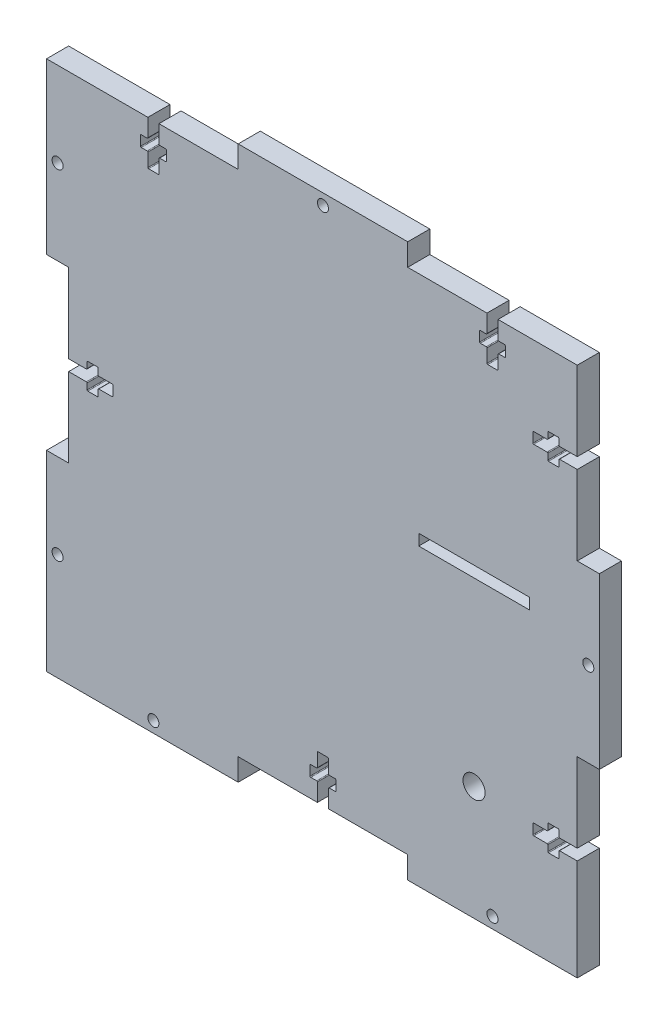
SolidWorks part; units mm, degrees
ref_plane "Front Plane" through (0, 0, 0) normal (0, 0, 1) x (1, 0, 0)
ref_plane "Top Plane" through (0, 0, 0) normal (0, 1, 0) x (1, 0, 0)
ref_plane "Right Plane" through (0, 0, 0) normal (1, 0, 0) x (0, 0, -1)
sketch "Sketch1" plane through (0, 0, 0) normal (0, 0, 1) x (1, 0, 0)
  line L0 (-69, 69) -> (-23, 69)
  line L5 (-75, -75) -> (75, -75) construction
  line L6 (-75, -75) -> (-75, 75) construction
  line L7 (-75, 75) -> (75, 75) construction
  line L8 (75, -75) -> (75, 75) construction
  line L9 (75, 23) -> (69, 23)
  line L10 (69, -23) -> (75, -23)
  line L11 (-69, -69) -> (69, -69) construction
  line L12 (-69, -69) -> (-69, 69) construction
  line L13 (-69, 69) -> (69, 69) construction
  line L14 (69, -69) -> (69, 69) construction
  line L15 (-69, -69) -> (69, 69) construction
  line L16 (69, -69) -> (69, -23)
  line L17 (-23, 69) -> (-23, 75)
  line L18 (-23, 75) -> (23, 75)
  line L19 (23, 75) -> (23, 69)
  line L20 (23, 69) -> (69, 69)
  line L21 (75, -23) -> (75, 23)
  line L22 (69, 23) -> (69, 69)
  line L23 (-75, 23) -> (-69, 23)
  line L24 (-69, 69) -> (-75, 69)
  line L25 (-75, 69) -> (-75, 23)
  line L26 (69, -69) -> (69, -75)
  line L27 (69, -75) -> (23, -75)
  line L28 (23, -75) -> (23, -69)
  line L29 (23, -69) -> (-23, -69)
  line L30 (-23, -69) -> (-23, -75)
  line L31 (-23, -75) -> (-69, -75)
  line L32 (-69, -75) -> (-69, -69) construction
  line L33 (-69, 23) -> (-69, -23)
  line L34 (-69, -23) -> (-75, -23)
  line L35 (-75, -23) -> (-75, -69)
  line L36 (-75, -69) -> (-69, -69) construction
  line L37 (-46, 69) -> (-46, -75) construction
  line L38 (-69, 69) -> (69, -69) construction
  line L39 (-75, -75) -> (-69, -75)
  line L40 (-75, -75) -> (-75, -69)
  point P0 (0, 0)
  point P6 (-7, -7)
  point P26 (0, -75)
  point P27 (-75, 0)
  dimension "D1" = 150
  dimension "D2" = 150
  dimension "D5" = 46
  dimension "D3" = 6
  dimension "D6" = 6
  dimension "D7" = 6
extrude "Box Side" add sketch "Sketch1" along normal blind 6
sketch "Sketch2" plane through (0, 0, 6) normal (0, 0, 1) x (1, 0, 0)
  line L0 (23, 72) -> (-23, 72) construction
  line L1 (23, 75) -> (23, 69) construction
  line L2 (-23, 69) -> (-23, 75) construction
  line L3 (-46, 69) -> (-46, -75) construction
  line L5 (0, 75) -> (0, 69) construction
  line L6 (-23, 75) -> (23, 75) construction
  line L7 (-69, 69) -> (69, 69) construction
  line L16 (-46, 69) -> (-46, -75) construction
  line L21 (0, -69) -> (0, 69) construction
  line L35 (-69, 69) -> (-23, 69) construction
  line L36 (-44.5, 69) -> (-44.5, 64.2)
  line L37 (-44.3, 64) -> (-42.7, 64)
  line L38 (-42.5, 63.8) -> (-42.5, 61.2)
  line L39 (-42.7, 61) -> (-44.3, 61)
  line L40 (-44.5, 60.8) -> (-44.5, 57.2)
  line L46 (-44.7, 57) -> (-47.3, 57)
  line L48 (-44.5, 69) -> (-47.5, 69)
  line L51 (-47.5, 60.8) -> (-47.5, 57.2)
  line L52 (-49.3, 61) -> (-47.7, 61)
  line L53 (-49.5, 63.8) -> (-49.5, 61.2)
  line L54 (-47.7, 64) -> (-49.3, 64)
  line L55 (-47.5, 69) -> (-47.5, 64.2)
  line L56 (47.5, 69) -> (47.5, 64.2)
  line L57 (47.7, 64) -> (49.3, 64)
  line L58 (49.5, 63.8) -> (49.5, 61.2)
  line L59 (49.3, 61) -> (47.7, 61)
  line L60 (47.5, 60.8) -> (47.5, 57.2)
  line L61 (44.5, 69) -> (47.5, 69)
  line L62 (44.7, 57) -> (47.3, 57)
  line L63 (44.5, 60.8) -> (44.5, 57.2)
  line L64 (42.7, 61) -> (44.3, 61)
  line L65 (42.5, 63.8) -> (42.5, 61.2)
  line L66 (44.3, 64) -> (42.7, 64)
  line L67 (44.5, 69) -> (44.5, 64.2)
  line L68 (-69, -69) -> (69, 69) construction
  line L69 (-69, -69) -> (69, 69) construction
  line L70 (75, 0) -> (69, 0) construction
  line L71 (72, 23) -> (72, -23) construction
  line L72 (69, 44.5) -> (64.2, 44.5)
  line L73 (64, 44.3) -> (64, 42.7)
  line L74 (63.8, 42.5) -> (61.2, 42.5)
  line L75 (61, 42.7) -> (61, 44.3)
  line L76 (60.8, 44.5) -> (57.2, 44.5)
  line L77 (57, 44.7) -> (57, 47.3)
  line L78 (69, 44.5) -> (69, 47.5)
  line L79 (60.8, 47.5) -> (57.2, 47.5)
  line L80 (61, 49.3) -> (61, 47.7)
  line L81 (63.8, 49.5) -> (61.2, 49.5)
  line L82 (64, 47.7) -> (64, 49.3)
  line L83 (69, 47.5) -> (64.2, 47.5)
  line L84 (69, -47.5) -> (64.2, -47.5)
  line L85 (64, -47.7) -> (64, -49.3)
  line L86 (63.8, -49.5) -> (61.2, -49.5)
  line L87 (61, -49.3) -> (61, -47.7)
  line L88 (60.8, -47.5) -> (57.2, -47.5)
  line L89 (69, -44.5) -> (69, -47.5)
  line L90 (57, -44.7) -> (57, -47.3)
  line L91 (60.8, -44.5) -> (57.2, -44.5)
  line L92 (61, -42.7) -> (61, -44.3)
  line L93 (63.8, -42.5) -> (61.2, -42.5)
  line L94 (64, -44.3) -> (64, -42.7)
  line L95 (69, -44.5) -> (64.2, -44.5)
  line L120 (-69, 69) -> (69, -69) construction
  line L121 (-69, 69) -> (69, -69) construction
  line L122 (-1.5, -69) -> (1.5, -69)
  line L123 (-23, -69) -> (23, -69) construction
  line L124 (1.5, -69) -> (1.5, -64.2)
  line L125 (1.7, -64) -> (3.3, -64)
  line L126 (3.5, -63.8) -> (3.5, -61.2)
  line L127 (3.3, -61) -> (1.7, -61)
  line L128 (1.5, -60.8) -> (1.5, -57.2)
  line L129 (1.3, -57) -> (-1.3, -57)
  line L130 (-1.5, -60.8) -> (-1.5, -57.2)
  line L131 (-3.3, -61) -> (-1.7, -61)
  line L132 (-3.5, -63.8) -> (-3.5, -61.2)
  line L133 (-1.7, -64) -> (-3.3, -64)
  line L134 (-1.5, -69) -> (-1.5, -64.2)
  line L135 (-69, -1.5) -> (-64.2, -1.5)
  line L136 (-64, -1.7) -> (-64, -3.3)
  line L137 (-63.8, -3.5) -> (-61.2, -3.5)
  line L138 (-61, -3.3) -> (-61, -1.7)
  line L139 (-60.8, -1.5) -> (-57.2, -1.5)
  line L140 (-57, 1.3) -> (-57, -1.3)
  line L141 (-60.8, 1.5) -> (-57.2, 1.5)
  line L142 (-61, 3.3) -> (-61, 1.7)
  line L143 (-63.8, 3.5) -> (-61.2, 3.5)
  line L144 (-64, 1.7) -> (-64, 3.3)
  line L145 (-69, 1.5) -> (-64.2, 1.5)
  line L146 (-69, -1.5) -> (-69, 1.5)
  line L147 (-69, -72) -> (-23, -72) construction
  line L148 (-23, 69) -> (-75, 69) construction
  line L149 (-23, -75) -> (-23, -69) construction
  line L150 (-69, -69) -> (-69, -75) construction
  line L151 (-75, -75) -> (-23, -75) construction
  circle A0 centre (0, 72) radius 1.5
  arc A1 (-44.5, 57.2) -> (-44.7, 57) centre (-44.7, 57.2) cw
  arc A2 (-44.3, 61) -> (-44.5, 60.8) centre (-44.3, 60.8) ccw
  arc A3 (-42.5, 61.2) -> (-42.7, 61) centre (-42.7, 61.2) cw
  arc A4 (-42.7, 64) -> (-42.5, 63.8) centre (-42.7, 63.8) cw
  arc A5 (-44.5, 64.2) -> (-44.3, 64) centre (-44.3, 64.2) ccw
  arc A6 (-47.5, 64.2) -> (-47.7, 64) centre (-47.7, 64.2) cw
  arc A7 (-49.3, 64) -> (-49.5, 63.8) centre (-49.3, 63.8) ccw
  arc A8 (-49.5, 61.2) -> (-49.3, 61) centre (-49.3, 61.2) ccw
  arc A9 (-47.7, 61) -> (-47.5, 60.8) centre (-47.7, 60.8) cw
  arc A10 (-47.5, 57.2) -> (-47.3, 57) centre (-47.3, 57.2) ccw
  arc A11 (47.5, 57.2) -> (47.3, 57) centre (47.3, 57.2) cw
  arc A12 (47.7, 61) -> (47.5, 60.8) centre (47.7, 60.8) ccw
  arc A13 (49.5, 61.2) -> (49.3, 61) centre (49.3, 61.2) cw
  arc A14 (49.3, 64) -> (49.5, 63.8) centre (49.3, 63.8) cw
  arc A15 (47.5, 64.2) -> (47.7, 64) centre (47.7, 64.2) ccw
  arc A16 (44.5, 64.2) -> (44.3, 64) centre (44.3, 64.2) cw
  arc A17 (42.7, 64) -> (42.5, 63.8) centre (42.7, 63.8) ccw
  arc A18 (42.5, 61.2) -> (42.7, 61) centre (42.7, 61.2) ccw
  arc A19 (44.3, 61) -> (44.5, 60.8) centre (44.3, 60.8) cw
  arc A20 (44.5, 57.2) -> (44.7, 57) centre (44.7, 57.2) ccw
  arc A21 (57.2, 44.5) -> (57, 44.7) centre (57.2, 44.7) cw
  arc A22 (61, 44.3) -> (60.8, 44.5) centre (60.8, 44.3) ccw
  arc A23 (61.2, 42.5) -> (61, 42.7) centre (61.2, 42.7) cw
  arc A24 (64, 42.7) -> (63.8, 42.5) centre (63.8, 42.7) cw
  arc A25 (64.2, 44.5) -> (64, 44.3) centre (64.2, 44.3) ccw
  arc A26 (64.2, 47.5) -> (64, 47.7) centre (64.2, 47.7) cw
  arc A27 (64, 49.3) -> (63.8, 49.5) centre (63.8, 49.3) ccw
  arc A28 (61.2, 49.5) -> (61, 49.3) centre (61.2, 49.3) ccw
  arc A29 (61, 47.7) -> (60.8, 47.5) centre (60.8, 47.7) cw
  arc A30 (57.2, 47.5) -> (57, 47.3) centre (57.2, 47.3) ccw
  arc A31 (57.2, -47.5) -> (57, -47.3) centre (57.2, -47.3) cw
  arc A32 (61, -47.7) -> (60.8, -47.5) centre (60.8, -47.7) ccw
  arc A33 (61.2, -49.5) -> (61, -49.3) centre (61.2, -49.3) cw
  arc A34 (64, -49.3) -> (63.8, -49.5) centre (63.8, -49.3) cw
  arc A35 (64.2, -47.5) -> (64, -47.7) centre (64.2, -47.7) ccw
  arc A36 (64.2, -44.5) -> (64, -44.3) centre (64.2, -44.3) cw
  arc A37 (64, -42.7) -> (63.8, -42.5) centre (63.8, -42.7) ccw
  arc A38 (61.2, -42.5) -> (61, -42.7) centre (61.2, -42.7) ccw
  arc A39 (61, -44.3) -> (60.8, -44.5) centre (60.8, -44.3) cw
  arc A40 (57.2, -44.5) -> (57, -44.7) centre (57.2, -44.7) ccw
  circle A41 centre (72, 0) radius 1.5
  arc A62 (1.5, -57.2) -> (1.3, -57) centre (1.3, -57.2) ccw
  arc A63 (1.7, -61) -> (1.5, -60.8) centre (1.7, -60.8) cw
  arc A64 (3.5, -61.2) -> (3.3, -61) centre (3.3, -61.2) ccw
  arc A65 (3.3, -64) -> (3.5, -63.8) centre (3.3, -63.8) ccw
  arc A66 (1.5, -64.2) -> (1.7, -64) centre (1.7, -64.2) cw
  arc A67 (-1.5, -64.2) -> (-1.7, -64) centre (-1.7, -64.2) ccw
  arc A68 (-3.3, -64) -> (-3.5, -63.8) centre (-3.3, -63.8) cw
  arc A69 (-3.5, -61.2) -> (-3.3, -61) centre (-3.3, -61.2) cw
  arc A70 (-1.7, -61) -> (-1.5, -60.8) centre (-1.7, -60.8) ccw
  arc A71 (-1.5, -57.2) -> (-1.3, -57) centre (-1.3, -57.2) cw
  arc A72 (-57.2, -1.5) -> (-57, -1.3) centre (-57.2, -1.3) ccw
  arc A73 (-61, -1.7) -> (-60.8, -1.5) centre (-60.8, -1.7) cw
  arc A74 (-61.2, -3.5) -> (-61, -3.3) centre (-61.2, -3.3) ccw
  arc A75 (-64, -3.3) -> (-63.8, -3.5) centre (-63.8, -3.3) ccw
  arc A76 (-64.2, -1.5) -> (-64, -1.7) centre (-64.2, -1.7) cw
  arc A77 (-64.2, 1.5) -> (-64, 1.7) centre (-64.2, 1.7) ccw
  arc A78 (-64, 3.3) -> (-63.8, 3.5) centre (-63.8, 3.3) cw
  arc A79 (-61.2, 3.5) -> (-61, 3.3) centre (-61.2, 3.3) cw
  arc A80 (-61, 1.7) -> (-60.8, 1.5) centre (-60.8, 1.7) ccw
  arc A81 (-57.2, 1.5) -> (-57, 1.3) centre (-57.2, 1.3) cw
  circle A82 centre (-46, -72) radius 1.5
  circle A83 centre (46, -72) radius 1.5
  circle A84 centre (-72, 46) radius 1.5
  circle A85 centre (-72, -46) radius 1.5
  point P6 (0, 72)
  point P38 (0, 0)
  point P56 (-46, 57)
  point P88 (46, 57)
  point P161 (57, 46)
  point P162 (57, -46)
  point P198 (0, -57)
  point P231 (-57, 0)
  point P234 (-42.5, 62.5)
  dimension "D1" = 3
  dimension "D2" = 0.2
  dimension "D8" = 0.2
  dimension "D14" = 3
  dimension "D4" = 3
  dimension "D7" = 1.5
  dimension "D10" = 3
  dimension "D12" = 1.5
  dimension "D9" = 12
  dimension "D11" = 5
  dimension "D13" = 7
  dimension "D3" = 12
  dimension "D5" = 7
  dimension "D6" = 5
extrude "Screw Cut-outs" cut sketch "Sketch2" against normal through all
sketch "Sketch3" plane through (0, 0, 6) normal (0, 0, 1) x (1, 0, 0)
  line L0 (23, -69) -> (50023, -69) construction
  line L1 (69, -44.5) -> (69, -23) construction
  line L2 (69, -75) -> (69, -47.5) construction
  line L4 (41, -41) -> (50041, -41) construction
  line L5 (41.5774, -47) -> (50041.5774, -47) construction
  line L8 (44, -52) -> (44, -50052) construction
  line L9 (69, -75) -> (69, -47.5) construction
  circle A0 centre (41, -44) radius 3
  circle A1 centre (41, -54) radius 15 construction
  point P15 (41, -54)
  point P16 (0, 0)
  point P17 (0, 0)
  point P20 (0, 0)
  dimension "D2" = 6
  dimension "D4" = 30
  dimension "D1" = 7
  dimension "D3" = 25
extrude "Cut-Extrude1" cut sketch "Sketch3" against normal through all
sketch "Sketch4" plane through (0, 0, 0) normal (0, 0, -1) x (-1, 0, 0)
  line L0 (-72, 1.5) -> (49928, 1.5) construction
  line L1 (-56, 8) -> (-26, 8)
  line L2 (-56, 8) -> (-56, 5)
  line L3 (-56, 5) -> (-26, 5)
  line L4 (-26, 8) -> (-26, 5)
  line L5 (-75, -23) -> (-75, 23) construction
  circle A1 centre (-72, 0) radius 1.5 construction
  dimension "D1" = 3.5
  dimension "D2" = 30
  dimension "D3" = 3
  dimension "D4" = 19
extrude "Cut-Extrude2" cut sketch "Sketch4" against normal up to surface (6 mm away) up to face at (44, -44, 6)
equation "\"filletRadius\"=0.2"
equation "\"D8@Sketch2\"=\"filletRadius\""
equation "\"D2@Sketch2\"=\"filletRadius\""
equation "\"fingerWidth\"= 46"
equation "\"D5@Sketch1\"=\"fingerWidth\""
equation "\"wallThickness\"= 6"
equation "\"D3@Sketch1\" = \"wallThickness\""
equation "\"D6@Sketch1\" = \"wallThickness\""
equation "\"D7@Sketch1\" = \"wallThickness\""
equation "\"D1@Box Side\" = \"wallThickness\""
equation "\"M3\"= 3"
equation "\"D14@Sketch2\"=\"M3\""
equation "\"D1@Sketch2\"=\"M3\""
equation "\"D12@Sketch2\"=\"M3\"/2"
equation "\"nutThickness\"=3"
equation "\"D10@Sketch2\" = \"nutThickness\""
equation "\"boltLength\"= 12"
equation "\"D9@Sketch2\" = \"boltLength\""
equation "\"distanceToNut\"= 5"
equation "\"D11@Sketch2\" = \"distanceToNut\""
equation "\"D13@Sketch2\" = \"nutWidth\""
equation "\"D7@Sketch2\"=\"M3\"/2"
equation "\"D4@Sketch2\" = \"nutThickness\""
equation "\"D3@Sketch2\" = \"boltLength\""
equation "\"D5@Sketch2\" = \"nutWidth\""
equation "\"D6@Sketch2\" = \"distanceToNut\""
equation "\"sideLength\"=150"
equation "\"D1@Sketch1\"=\"sideLength\""
equation "\"D2@Sketch1\"=\"sideLength\""
equation "\"nutWidth\"=7"
